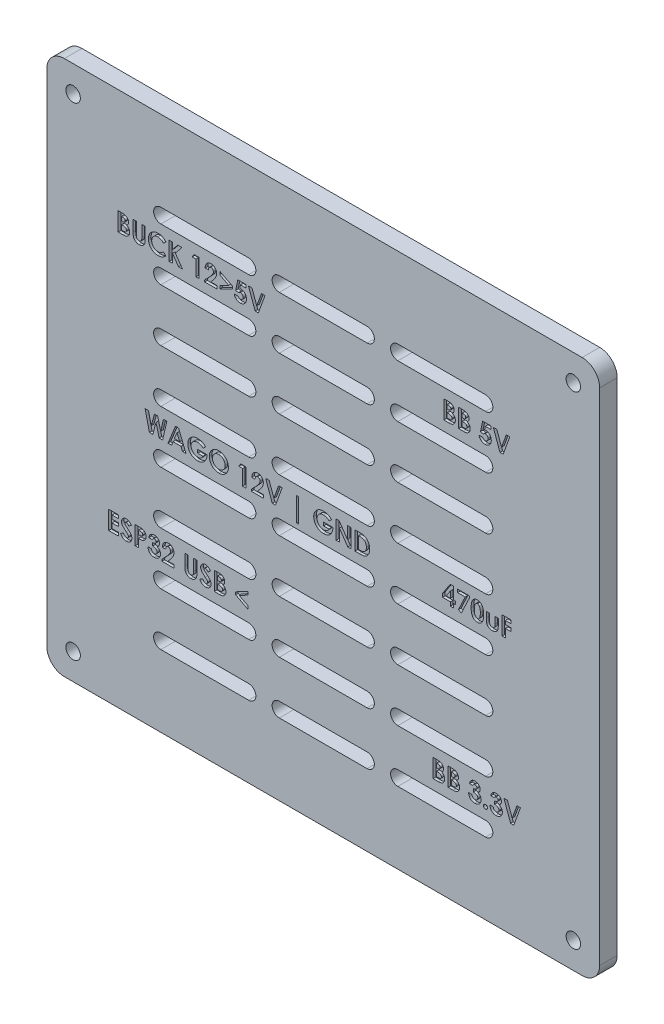
SolidWorks part; units mm, degrees
ref_plane "Front Plane" through (0, 0, 0) normal (0, 0, 1) x (1, 0, 0)
ref_plane "Top Plane" through (0, 0, 0) normal (0, 1, 0) x (1, 0, 0)
ref_plane "Right Plane" through (0, 0, 0) normal (1, 0, 0) x (0, 0, -1)
sketch "Sketch1" plane through (0, 0, 0) normal (0, 0, 1) x (1, 0, 0)
  line L0 (-59, 34) -> (59, 34)
  line L1 (63, 38) -> (63, 152)
  line L2 (59, 156) -> (-59, 156)
  line L3 (-63, 152) -> (-63, 38)
  arc A0 (-63, 38) -> (-59, 34) centre (-59, 38) ccw
  arc A1 (59, 34) -> (63, 38) centre (59, 38) ccw
  arc A2 (63, 152) -> (59, 156) centre (59, 152) ccw
  arc A3 (-59, 156) -> (-63, 152) centre (-59, 152) ccw
extrude "Plate" add sketch "Sketch1" along normal blind 4
sketch "Sketch2" plane through (0, 0, 0) normal (0, 0, 1) x (1, 0, 0)
  line L0 (-37, 52) -> (-17, 52) construction
  line L1 (-37, 53.65) -> (-17, 53.65)
  line L2 (-37, 50.35) -> (-17, 50.35)
  line L3 (-10, 52) -> (10, 52) construction
  line L4 (-10, 53.65) -> (10, 53.65)
  line L5 (-10, 50.35) -> (10, 50.35)
  line L6 (17, 52) -> (37, 52) construction
  line L7 (17, 53.65) -> (37, 53.65)
  line L8 (17, 50.35) -> (37, 50.35)
  line L9 (-37, 64) -> (-17, 64) construction
  line L10 (-37, 65.65) -> (-17, 65.65)
  line L11 (-37, 62.35) -> (-17, 62.35)
  line L12 (-10, 64) -> (10, 64) construction
  line L13 (-10, 65.65) -> (10, 65.65)
  line L14 (-10, 62.35) -> (10, 62.35)
  line L15 (17, 64) -> (37, 64) construction
  line L16 (17, 65.65) -> (37, 65.65)
  line L17 (17, 62.35) -> (37, 62.35)
  line L18 (-37, 76) -> (-17, 76) construction
  line L19 (-37, 77.65) -> (-17, 77.65)
  line L20 (-37, 74.35) -> (-17, 74.35)
  line L21 (-10, 76) -> (10, 76) construction
  line L22 (-10, 77.65) -> (10, 77.65)
  line L23 (-10, 74.35) -> (10, 74.35)
  line L24 (17, 76) -> (37, 76) construction
  line L25 (17, 77.65) -> (37, 77.65)
  line L26 (17, 74.35) -> (37, 74.35)
  line L27 (-37, 88) -> (-17, 88) construction
  line L28 (-37, 89.65) -> (-17, 89.65)
  line L29 (-37, 86.35) -> (-17, 86.35)
  line L30 (-10, 88) -> (10, 88) construction
  line L31 (-10, 89.65) -> (10, 89.65)
  line L32 (-10, 86.35) -> (10, 86.35)
  line L33 (17, 88) -> (37, 88) construction
  line L34 (17, 89.65) -> (37, 89.65)
  line L35 (17, 86.35) -> (37, 86.35)
  line L36 (-37, 100) -> (-17, 100) construction
  line L37 (-37, 101.65) -> (-17, 101.65)
  line L38 (-37, 98.35) -> (-17, 98.35)
  line L39 (-10, 100) -> (10, 100) construction
  line L40 (-10, 101.65) -> (10, 101.65)
  line L41 (-10, 98.35) -> (10, 98.35)
  line L42 (17, 100) -> (37, 100) construction
  line L43 (17, 101.65) -> (37, 101.65)
  line L44 (17, 98.35) -> (37, 98.35)
  line L45 (-37, 112) -> (-17, 112) construction
  line L46 (-37, 113.65) -> (-17, 113.65)
  line L47 (-37, 110.35) -> (-17, 110.35)
  line L48 (-10, 112) -> (10, 112) construction
  line L49 (-10, 113.65) -> (10, 113.65)
  line L50 (-10, 110.35) -> (10, 110.35)
  line L51 (17, 112) -> (37, 112) construction
  line L52 (17, 113.65) -> (37, 113.65)
  line L53 (17, 110.35) -> (37, 110.35)
  line L54 (-37, 124) -> (-17, 124) construction
  line L55 (-37, 125.65) -> (-17, 125.65)
  line L56 (-37, 122.35) -> (-17, 122.35)
  line L57 (-10, 124) -> (10, 124) construction
  line L58 (-10, 125.65) -> (10, 125.65)
  line L59 (-10, 122.35) -> (10, 122.35)
  line L60 (17, 124) -> (37, 124) construction
  line L61 (17, 125.65) -> (37, 125.65)
  line L62 (17, 122.35) -> (37, 122.35)
  line L63 (-37, 136) -> (-17, 136) construction
  line L64 (-37, 137.65) -> (-17, 137.65)
  line L65 (-37, 134.35) -> (-17, 134.35)
  line L66 (-10, 136) -> (10, 136) construction
  line L67 (-10, 137.65) -> (10, 137.65)
  line L68 (-10, 134.35) -> (10, 134.35)
  line L69 (17, 136) -> (37, 136) construction
  line L70 (17, 137.65) -> (37, 137.65)
  line L71 (17, 134.35) -> (37, 134.35)
  circle A0 centre (-57, 40) radius 1.65
  circle A1 centre (57, 40) radius 1.65
  circle A2 centre (-57, 150) radius 1.65
  circle A3 centre (57, 150) radius 1.65
  arc A4 (-37, 53.65) -> (-37, 50.35) centre (-37, 52) ccw
  arc A5 (-17, 50.35) -> (-17, 53.65) centre (-17, 52) ccw
  arc A6 (-10, 53.65) -> (-10, 50.35) centre (-10, 52) ccw
  arc A7 (10, 50.35) -> (10, 53.65) centre (10, 52) ccw
  arc A8 (17, 53.65) -> (17, 50.35) centre (17, 52) ccw
  arc A9 (37, 50.35) -> (37, 53.65) centre (37, 52) ccw
  arc A10 (-37, 65.65) -> (-37, 62.35) centre (-37, 64) ccw
  arc A11 (-17, 62.35) -> (-17, 65.65) centre (-17, 64) ccw
  arc A12 (-10, 65.65) -> (-10, 62.35) centre (-10, 64) ccw
  arc A13 (10, 62.35) -> (10, 65.65) centre (10, 64) ccw
  arc A14 (17, 65.65) -> (17, 62.35) centre (17, 64) ccw
  arc A15 (37, 62.35) -> (37, 65.65) centre (37, 64) ccw
  arc A16 (-37, 77.65) -> (-37, 74.35) centre (-37, 76) ccw
  arc A17 (-17, 74.35) -> (-17, 77.65) centre (-17, 76) ccw
  arc A18 (-10, 77.65) -> (-10, 74.35) centre (-10, 76) ccw
  arc A19 (10, 74.35) -> (10, 77.65) centre (10, 76) ccw
  arc A20 (17, 77.65) -> (17, 74.35) centre (17, 76) ccw
  arc A21 (37, 74.35) -> (37, 77.65) centre (37, 76) ccw
  arc A22 (-37, 89.65) -> (-37, 86.35) centre (-37, 88) ccw
  arc A23 (-17, 86.35) -> (-17, 89.65) centre (-17, 88) ccw
  arc A24 (-10, 89.65) -> (-10, 86.35) centre (-10, 88) ccw
  arc A25 (10, 86.35) -> (10, 89.65) centre (10, 88) ccw
  arc A26 (17, 89.65) -> (17, 86.35) centre (17, 88) ccw
  arc A27 (37, 86.35) -> (37, 89.65) centre (37, 88) ccw
  arc A28 (-37, 101.65) -> (-37, 98.35) centre (-37, 100) ccw
  arc A29 (-17, 98.35) -> (-17, 101.65) centre (-17, 100) ccw
  arc A30 (-10, 101.65) -> (-10, 98.35) centre (-10, 100) ccw
  arc A31 (10, 98.35) -> (10, 101.65) centre (10, 100) ccw
  arc A32 (17, 101.65) -> (17, 98.35) centre (17, 100) ccw
  arc A33 (37, 98.35) -> (37, 101.65) centre (37, 100) ccw
  arc A34 (-37, 113.65) -> (-37, 110.35) centre (-37, 112) ccw
  arc A35 (-17, 110.35) -> (-17, 113.65) centre (-17, 112) ccw
  arc A36 (-10, 113.65) -> (-10, 110.35) centre (-10, 112) ccw
  arc A37 (10, 110.35) -> (10, 113.65) centre (10, 112) ccw
  arc A38 (17, 113.65) -> (17, 110.35) centre (17, 112) ccw
  arc A39 (37, 110.35) -> (37, 113.65) centre (37, 112) ccw
  arc A40 (-37, 125.65) -> (-37, 122.35) centre (-37, 124) ccw
  arc A41 (-17, 122.35) -> (-17, 125.65) centre (-17, 124) ccw
  arc A42 (-10, 125.65) -> (-10, 122.35) centre (-10, 124) ccw
  arc A43 (10, 122.35) -> (10, 125.65) centre (10, 124) ccw
  arc A44 (17, 125.65) -> (17, 122.35) centre (17, 124) ccw
  arc A45 (37, 122.35) -> (37, 125.65) centre (37, 124) ccw
  arc A46 (-37, 137.65) -> (-37, 134.35) centre (-37, 136) ccw
  arc A47 (-17, 134.35) -> (-17, 137.65) centre (-17, 136) ccw
  arc A48 (-10, 137.65) -> (-10, 134.35) centre (-10, 136) ccw
  arc A49 (10, 134.35) -> (10, 137.65) centre (10, 136) ccw
  arc A50 (17, 137.65) -> (17, 134.35) centre (17, 136) ccw
  arc A51 (37, 134.35) -> (37, 137.65) centre (37, 136) ccw
  point P10 (-27, 52)
  point P15 (0, 52)
  point P22 (27, 52)
  point P29 (-27, 64)
  point P36 (0, 64)
  point P43 (27, 64)
  point P50 (-27, 76)
  point P57 (0, 76)
  point P64 (27, 76)
  point P71 (-27, 88)
  point P78 (0, 88)
  point P85 (27, 88)
  point P92 (-27, 100)
  point P99 (0, 100)
  point P106 (27, 100)
  point P113 (-27, 112)
  point P120 (0, 112)
  point P127 (27, 112)
  point P134 (-27, 124)
  point P141 (0, 124)
  point P148 (27, 124)
  point P155 (-27, 136)
  point P162 (0, 136)
  point P169 (27, 136)
  point P176 (0, 0)
extrude "Mounting slots" cut sketch "Sketch2" along normal through all
ref_plane "P1_Front_4" through (0, 0, 4) normal (0, 0, 1) x (1, 0, 0)
sketch "Sketch3" plane through (0, 0, 4) normal (0, 0, 1) x (1, 0, 0)
  text T0 "BUCK 12>5V" font "Century Gothic" height 4.2
  text T1 "BB 5V" font "Century Gothic" height 4.2
  text T2 "WAGO 12V | GND" font "Century Gothic" height 4.2
  text T3 "470uF" font "Century Gothic" height 4.2
  text T4 "ESP32 USB <" font "Century Gothic" height 4.2
  text T5 "BB 3.3V" font "Century Gothic" height 4.2
extrude "Zone labels" cut sketch "Sketch3" against normal blind 0.6
